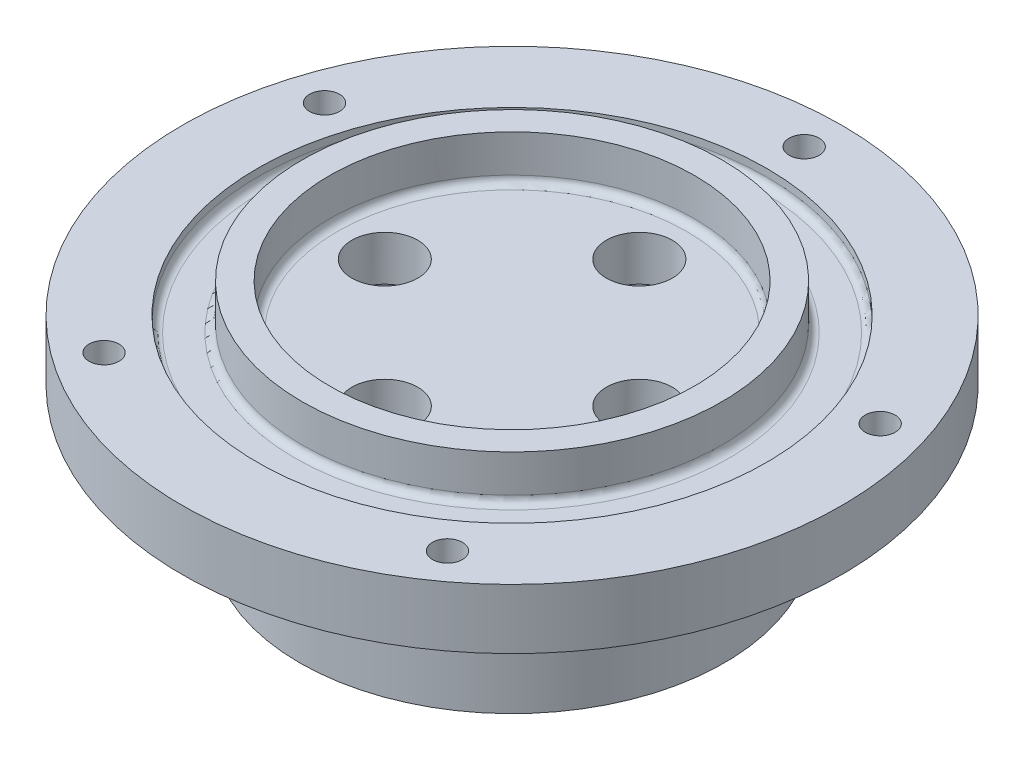
SolidWorks part; units mm, degrees
material "ASTM A36 Steel"
ref_plane "Front Plane" through (0, 0, 0) normal (0, 0, 1) x (1, 0, 0)
ref_plane "Top Plane" through (0, 0, 0) normal (0, 1, 0) x (1, 0, 0)
ref_plane "Right Plane" through (0, 0, 0) normal (1, 0, 0) x (0, 0, -1)
sketch "Sketch1" plane through (0, 0, 0) normal (0, 0, 1) x (1, 0, 0)
  line L0 (19.3357, -14.2875) -> (19.3357, 0)
  line L1 (55, 0) -> (-55, 0) construction
  line L2 (19.3357, 0) -> (0, 0)
  line L3 (0, 0) -> (0, 20.0604) construction
  line L4 (0, 4.7625) -> (19.3357, 4.7625)
  line L5 (19.3357, 4.7625) -> (19.3357, 9.525)
  line L6 (19.3357, 9.525) -> (22.225, 9.525)
  line L7 (22.225, 9.525) -> (22.225, 4.7625)
  line L8 (22.225, 4.7625) -> (26.9875, 4.7625)
  line L9 (34.925, 6.35) -> (34.925, 0)
  line L10 (34.925, 0) -> (22.5107, 0)
  line L11 (22.5107, 0) -> (22.5107, -14.2875)
  line L12 (22.5107, -14.2875) -> (19.3357, -14.2875)
  line L13 (26.9875, 4.7625) -> (26.9875, 6.35)
  line L14 (26.9875, 6.35) -> (34.925, 6.35)
  line L15 (0, 4.7625) -> (0, 0)
  dimension "D2" = 44.45
  dimension "D3" = 69.85
  dimension "D4" = 14.2875
  dimension "D5" = 14.2875
  dimension "D6" = 1.5875
  dimension "D7" = 4.7625
  dimension "D8" = 3.175
  dimension "D9" = 6.35
  dimension "D10" = 3.175
  dimension "D11" = 4.7625
  dimension "D12" = 2.8892
revolve "Revolve1" add sketch "Sketch1" angle 360 mid plane about L3
sketch "Sketch2" plane through (0, 4.7625, 0) normal (0, 1, 0) x (1, 0, 0)
  line L0 (13.4874, 0) -> (-13.4874, 0)
  line L1 (0, -13.4874) -> (0, 13.4874)
  circle A0 centre (-13.4874, 0) radius 3.4925
  circle A1 centre (0, 13.4874) radius 3.4925
  circle A2 centre (13.4874, 0) radius 3.4925
  circle A3 centre (0, -13.4874) radius 3.4925
  point P8 (0, 0)
  dimension "D2" = 6.985
  dimension "D1" = 13.4874
extrude "Cut-Extrude1" cut sketch "Sketch2" against normal through all contours A0 | A3 | A2 | A1
sketch "Sketch3" plane through (0, 6.35, 0) normal (0, 1, 0) x (1, 0, 0)
  line L0 (0, 34.925) -> (0, 26.9875) construction
  circle A0 centre (0, 0) radius 34.925 construction
  circle A1 centre (0, 0) radius 26.9875 construction
  circle A2 centre (0, 30.9562) radius 1.5875
  dimension "D1" = 3.175
extrude "Cut-Extrude2" cut sketch "Sketch3" against normal through all
ref_axis "Axis1" through (0, 14.7638, 0) along (0, -1, 0)
pattern_circular "CirPattern1" count 5 over 360 about axis through (0, 14.7638, 0) along (0, -1, 0) of "Cut-Extrude2"
fillet "Fillet1" radius 0.7937 4 edges at (0, 4.7625, -22.225) (0, 4.7625, -26.9875) (0, 4.7625, -19.3357) (0, 0, -19.3357)
